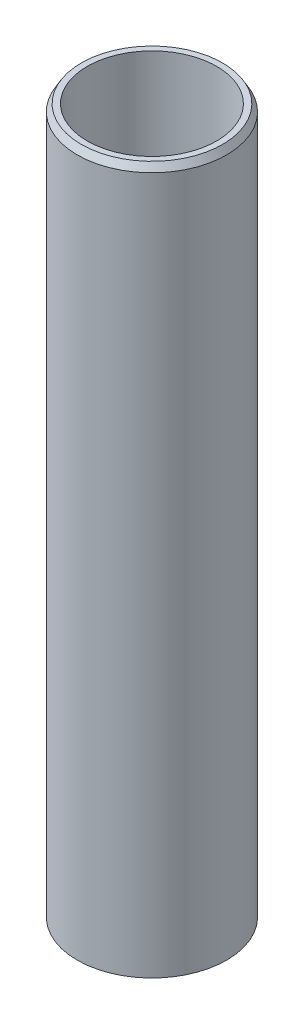
SolidWorks part; units mm, degrees
ref_plane "Front Plane" through (0, 0, 0) normal (0, 0, 1) x (1, 0, 0)
ref_plane "Top Plane" through (0, 0, 0) normal (0, 1, 0) x (1, 0, 0)
ref_plane "Right Plane" through (0, 0, 0) normal (1, 0, 0) x (0, 0, -1)
sketch "Sketch1" plane through (0, 0, 0) normal (0, 1, 0) x (1, 0, 0)
  circle A0 centre (0, 0) radius 57.5
  dimension "SHAFT_OD" = 115
extrude "Boss-Extrude1" add sketch "Sketch1" along normal blind 545.3142
sketch "Sketch2" plane through (0, 0, 0) normal (0, 1, 0) x (1, 0, 0)
  circle A0 centre (0, 0) radius 49.7992
  dimension "BORE_D" = 99.5985
extrude "Cut-Extrude1" cut sketch "Sketch2" along normal through all
chamfer "Chamfer1" distance 5.428 angle 30 2 edges at (0, 545.3142, 57.5) (0, 0, 57.5) first distance on face at (0, 545.3142, 57.5) first distance on face at (0, 0, 49.7992)
